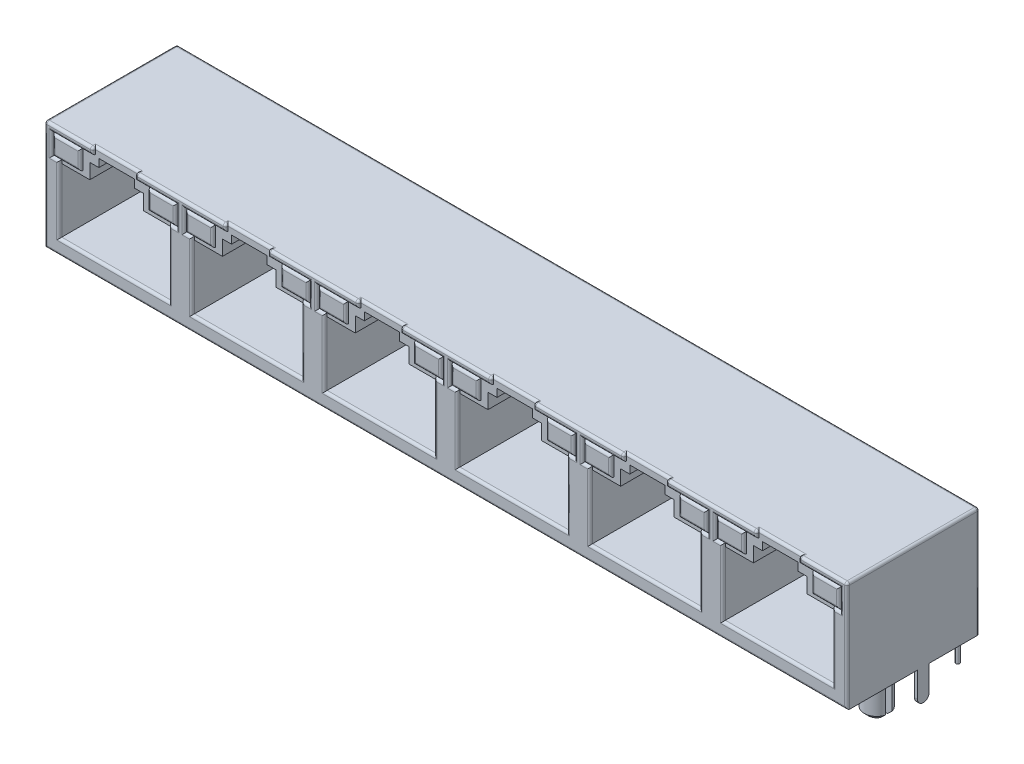
SolidWorks part; units mm, degrees
ref_plane "前视基准面" through (0, 0, 0) normal (0, 0, 1) x (1, 0, 0)
ref_plane "上视基准面" through (0, 0, 0) normal (0, 1, 0) x (1, 0, 0)
ref_plane "右视基准面" through (0, 0, 0) normal (1, 0, 0) x (0, 0, -1)
sketch "草图1" plane through (0, 0, 0) normal (0, 1, 0) x (1, 0, 0)
  line L0 (15.2703, 0) -> (110.5203, 0)
  line L1 (110.5203, 0) -> (110.5203, 15.7)
  line L2 (110.5203, 15.7) -> (15.2703, 15.7)
  line L3 (15.2703, 15.7) -> (15.2703, 0)
extrude "凸台-拉伸1" add sketch "草图1" along normal blind 13.05
sketch "草图2" plane through (0, 0, 0) normal (0, -1, 0) x (1, 0, 0)
  circle A0 centre (17.1703, -5.4) radius 1.48
  circle A1 centre (108.6203, -5.4) radius 1.48
extrude "凸台-拉伸2" add sketch "草图2" along normal blind 3.7
sketch "草图3" plane through (0, 0, 0) normal (0, 0, 1) x (1, 0, 0)
  line L0 (64.2703, 1.76) -> (77.2703, 1.76)
  line L3 (72.8703, 12.05) -> (68.6703, 12.05)
  line L4 (68.6703, 12.05) -> (68.6703, 11.11)
  line L5 (68.6703, 11.11) -> (67.5953, 11.11)
  line L6 (67.5953, 11.11) -> (67.5953, 9.32)
  line L7 (67.5953, 9.32) -> (64.2703, 9.32)
  line L8 (77.2703, 1.76) -> (77.2703, 9.32)
  line L10 (64.2703, 1.76) -> (64.2703, 9.32)
  line L11 (73.9453, 9.32) -> (77.2703, 9.32)
  line L12 (73.9453, 11.11) -> (73.9453, 9.32)
  line L13 (72.8703, 11.11) -> (73.9453, 11.11)
  line L14 (72.8703, 12.05) -> (72.8703, 11.11)
  line L15 (80.0203, 1.76) -> (93.0203, 1.76)
  line L16 (88.6203, 12.05) -> (84.4203, 12.05)
  line L17 (84.4203, 12.05) -> (84.4203, 11.11)
  line L18 (84.4203, 11.11) -> (83.3453, 11.11)
  line L19 (83.3453, 11.11) -> (83.3453, 9.32)
  line L20 (83.3453, 9.32) -> (80.0203, 9.32)
  line L21 (93.0203, 1.76) -> (93.0203, 9.32)
  line L22 (80.0203, 1.76) -> (80.0203, 9.32)
  line L23 (89.6953, 9.32) -> (93.0203, 9.32)
  line L24 (89.6953, 11.11) -> (89.6953, 9.32)
  line L25 (88.6203, 11.11) -> (89.6953, 11.11)
  line L26 (88.6203, 12.05) -> (88.6203, 11.11)
  line L27 (95.7703, 1.76) -> (108.7703, 1.76)
  line L28 (104.3703, 12.05) -> (100.1703, 12.05)
  line L29 (100.1703, 12.05) -> (100.1703, 11.11)
  line L30 (100.1703, 11.11) -> (99.0953, 11.11)
  line L31 (99.0953, 11.11) -> (99.0953, 9.32)
  line L32 (99.0953, 9.32) -> (95.7703, 9.32)
  line L33 (108.7703, 1.76) -> (108.7703, 9.32)
  line L34 (95.7703, 1.76) -> (95.7703, 9.32)
  line L35 (105.4453, 9.32) -> (108.7703, 9.32)
  line L36 (105.4453, 11.11) -> (105.4453, 9.32)
  line L37 (104.3703, 11.11) -> (105.4453, 11.11)
  line L38 (104.3703, 12.05) -> (104.3703, 11.11)
  line L39 (48.5203, 1.76) -> (61.5203, 1.76)
  line L40 (57.1203, 12.05) -> (52.9203, 12.05)
  line L41 (52.9203, 12.05) -> (52.9203, 11.11)
  line L42 (52.9203, 11.11) -> (51.8453, 11.11)
  line L43 (51.8453, 11.11) -> (51.8453, 9.32)
  line L44 (51.8453, 9.32) -> (48.5203, 9.32)
  line L45 (61.5203, 1.76) -> (61.5203, 9.32)
  line L46 (48.5203, 1.76) -> (48.5203, 9.32)
  line L47 (58.1953, 9.32) -> (61.5203, 9.32)
  line L48 (58.1953, 11.11) -> (58.1953, 9.32)
  line L49 (57.1203, 11.11) -> (58.1953, 11.11)
  line L50 (57.1203, 12.05) -> (57.1203, 11.11)
  line L51 (32.7703, 1.76) -> (45.7703, 1.76)
  line L52 (41.3703, 12.05) -> (37.1703, 12.05)
  line L53 (37.1703, 12.05) -> (37.1703, 11.11)
  line L54 (37.1703, 11.11) -> (36.0953, 11.11)
  line L55 (36.0953, 11.11) -> (36.0953, 9.32)
  line L56 (36.0953, 9.32) -> (32.7703, 9.32)
  line L57 (45.7703, 1.76) -> (45.7703, 9.32)
  line L58 (32.7703, 1.76) -> (32.7703, 9.32)
  line L59 (42.4453, 9.32) -> (45.7703, 9.32)
  line L60 (42.4453, 11.11) -> (42.4453, 9.32)
  line L61 (41.3703, 11.11) -> (42.4453, 11.11)
  line L62 (41.3703, 12.05) -> (41.3703, 11.11)
  line L63 (17.0203, 1.76) -> (30.0203, 1.76)
  line L64 (25.6203, 12.05) -> (21.4203, 12.05)
  line L65 (21.4203, 12.05) -> (21.4203, 11.11)
  line L66 (21.4203, 11.11) -> (20.3453, 11.11)
  line L67 (20.3453, 11.11) -> (20.3453, 9.32)
  line L68 (20.3453, 9.32) -> (17.0203, 9.32)
  line L69 (30.0203, 1.76) -> (30.0203, 9.32)
  line L70 (17.0203, 1.76) -> (17.0203, 9.32)
  line L71 (26.6953, 9.32) -> (30.0203, 9.32)
  line L72 (26.6953, 11.11) -> (26.6953, 9.32)
  line L73 (25.6203, 11.11) -> (26.6953, 11.11)
  line L74 (25.6203, 12.05) -> (25.6203, 11.11)
  dimension "D1" = 3
  dimension "D2" = 4
extrude "切除-拉伸1" cut sketch "草图3" against normal blind 13
sketch "草图4" plane through (0, 0, 0) normal (0, 0, 1) x (1, 0, 0)
  line L0 (21.0203, 13.05) -> (26.0203, 13.05)
  line L1 (15.2703, 13.05) -> (110.5203, 13.05) construction
  line L2 (26.0203, 12.25) -> (30.9203, 12.25)
  line L3 (30.9203, 12.25) -> (30.9203, 9.73)
  line L4 (30.9203, 9.73) -> (30.0203, 9.73)
  line L5 (30.0203, 9.73) -> (30.0203, 9.32)
  line L6 (17.0203, 9.32) -> (30.0203, 9.32)
  line L7 (26.0203, 13.05) -> (26.0203, 12.25)
  line L8 (21.0203, 13.05) -> (21.0203, 12.25)
  line L9 (17.0203, 9.73) -> (17.0203, 9.32)
  line L10 (16.1203, 9.73) -> (17.0203, 9.73)
  line L11 (16.1203, 12.25) -> (16.1203, 9.73)
  line L12 (21.0203, 12.25) -> (16.1203, 12.25)
  line L13 (36.7703, 13.05) -> (41.7703, 13.05)
  line L14 (41.7703, 12.25) -> (46.6703, 12.25)
  line L15 (46.6703, 12.25) -> (46.6703, 9.73)
  line L16 (46.6703, 9.73) -> (45.7703, 9.73)
  line L17 (45.7703, 9.73) -> (45.7703, 9.32)
  line L18 (32.7703, 9.32) -> (45.7703, 9.32)
  line L19 (41.7703, 13.05) -> (41.7703, 12.25)
  line L20 (36.7703, 13.05) -> (36.7703, 12.25)
  line L21 (32.7703, 9.73) -> (32.7703, 9.32)
  line L22 (31.8703, 9.73) -> (32.7703, 9.73)
  line L23 (31.8703, 12.25) -> (31.8703, 9.73)
  line L24 (36.7703, 12.25) -> (31.8703, 12.25)
  line L25 (52.5203, 13.05) -> (57.5203, 13.05)
  line L26 (57.5203, 12.25) -> (62.4203, 12.25)
  line L27 (62.4203, 12.25) -> (62.4203, 9.73)
  line L28 (62.4203, 9.73) -> (61.5203, 9.73)
  line L29 (61.5203, 9.73) -> (61.5203, 9.32)
  line L30 (48.5203, 9.32) -> (61.5203, 9.32)
  line L31 (57.5203, 13.05) -> (57.5203, 12.25)
  line L32 (52.5203, 13.05) -> (52.5203, 12.25)
  line L33 (48.5203, 9.73) -> (48.5203, 9.32)
  line L34 (47.6203, 9.73) -> (48.5203, 9.73)
  line L35 (47.6203, 12.25) -> (47.6203, 9.73)
  line L36 (52.5203, 12.25) -> (47.6203, 12.25)
  line L37 (68.2703, 13.05) -> (73.2703, 13.05)
  line L38 (73.2703, 12.25) -> (78.1703, 12.25)
  line L39 (78.1703, 12.25) -> (78.1703, 9.73)
  line L40 (78.1703, 9.73) -> (77.2703, 9.73)
  line L41 (77.2703, 9.73) -> (77.2703, 9.32)
  line L42 (64.2703, 9.32) -> (77.2703, 9.32)
  line L43 (73.2703, 13.05) -> (73.2703, 12.25)
  line L44 (68.2703, 13.05) -> (68.2703, 12.25)
  line L45 (64.2703, 9.73) -> (64.2703, 9.32)
  line L46 (63.3703, 9.73) -> (64.2703, 9.73)
  line L47 (63.3703, 12.25) -> (63.3703, 9.73)
  line L48 (68.2703, 12.25) -> (63.3703, 12.25)
  line L49 (84.0203, 13.05) -> (89.0203, 13.05)
  line L50 (89.0203, 12.25) -> (93.9203, 12.25)
  line L51 (93.9203, 12.25) -> (93.9203, 9.73)
  line L52 (93.9203, 9.73) -> (93.0203, 9.73)
  line L53 (93.0203, 9.73) -> (93.0203, 9.32)
  line L54 (80.0203, 9.32) -> (93.0203, 9.32)
  line L55 (89.0203, 13.05) -> (89.0203, 12.25)
  line L56 (84.0203, 13.05) -> (84.0203, 12.25)
  line L57 (80.0203, 9.73) -> (80.0203, 9.32)
  line L58 (79.1203, 9.73) -> (80.0203, 9.73)
  line L59 (79.1203, 12.25) -> (79.1203, 9.73)
  line L60 (84.0203, 12.25) -> (79.1203, 12.25)
  line L61 (99.7703, 13.05) -> (104.7703, 13.05)
  line L62 (104.7703, 12.25) -> (109.6703, 12.25)
  line L63 (109.6703, 12.25) -> (109.6703, 9.73)
  line L64 (109.6703, 9.73) -> (108.7703, 9.73)
  line L65 (108.7703, 9.73) -> (108.7703, 9.32)
  line L66 (95.7703, 9.32) -> (108.7703, 9.32)
  line L67 (104.7703, 13.05) -> (104.7703, 12.25)
  line L68 (99.7703, 13.05) -> (99.7703, 12.25)
  line L69 (95.7703, 9.73) -> (95.7703, 9.32)
  line L70 (94.8703, 9.73) -> (95.7703, 9.73)
  line L71 (94.8703, 12.25) -> (94.8703, 9.73)
  line L72 (99.7703, 12.25) -> (94.8703, 12.25)
  dimension "D1" = 6
extrude "切除-拉伸2" cut sketch "草图4" against normal blind 0.3
sketch "草图5" plane through (0, 0, -0.3) normal (0, 0, 1) x (1, 0, 0)
  line L1 (46.5703, 9.85) -> (46.5703, 12.15)
  line L6 (30.8203, 9.85) -> (30.8203, 12.15)
  line L7 (27.5203, 9.85) -> (30.8203, 9.85)
  line L8 (27.5203, 12.15) -> (27.5203, 9.85)
  line L9 (16.2203, 12.15) -> (19.5203, 12.15)
  line L10 (19.5203, 12.15) -> (19.5203, 9.85)
  line L11 (19.5203, 9.85) -> (16.2203, 9.85)
  line L12 (16.2203, 9.85) -> (16.2203, 12.15)
  line L13 (30.8203, 12.15) -> (27.5203, 12.15)
  line L14 (43.2703, 9.85) -> (46.5703, 9.85)
  line L15 (43.2703, 12.15) -> (43.2703, 9.85)
  line L16 (31.9703, 12.15) -> (35.2703, 12.15)
  line L17 (35.2703, 12.15) -> (35.2703, 9.85)
  line L18 (35.2703, 9.85) -> (31.9703, 9.85)
  line L19 (31.9703, 9.85) -> (31.9703, 12.15)
  line L20 (46.5703, 12.15) -> (43.2703, 12.15)
  line L21 (62.3203, 9.85) -> (62.3203, 12.15)
  line L22 (59.0203, 9.85) -> (62.3203, 9.85)
  line L23 (59.0203, 12.15) -> (59.0203, 9.85)
  line L24 (47.7203, 12.15) -> (51.0203, 12.15)
  line L25 (51.0203, 12.15) -> (51.0203, 9.85)
  line L26 (51.0203, 9.85) -> (47.7203, 9.85)
  line L27 (47.7203, 9.85) -> (47.7203, 12.15)
  line L28 (62.3203, 12.15) -> (59.0203, 12.15)
  line L29 (78.0703, 9.85) -> (78.0703, 12.15)
  line L30 (74.7703, 9.85) -> (78.0703, 9.85)
  line L31 (74.7703, 12.15) -> (74.7703, 9.85)
  line L32 (63.4703, 12.15) -> (66.7703, 12.15)
  line L33 (66.7703, 12.15) -> (66.7703, 9.85)
  line L34 (66.7703, 9.85) -> (63.4703, 9.85)
  line L35 (63.4703, 9.85) -> (63.4703, 12.15)
  line L36 (78.0703, 12.15) -> (74.7703, 12.15)
  line L37 (93.8203, 9.85) -> (93.8203, 12.15)
  line L38 (90.5203, 9.85) -> (93.8203, 9.85)
  line L39 (90.5203, 12.15) -> (90.5203, 9.85)
  line L40 (79.2203, 12.15) -> (82.5203, 12.15)
  line L41 (82.5203, 12.15) -> (82.5203, 9.85)
  line L42 (82.5203, 9.85) -> (79.2203, 9.85)
  line L43 (79.2203, 9.85) -> (79.2203, 12.15)
  line L44 (93.8203, 12.15) -> (90.5203, 12.15)
  line L45 (109.5703, 9.85) -> (109.5703, 12.15)
  line L46 (106.2703, 9.85) -> (109.5703, 9.85)
  line L47 (106.2703, 12.15) -> (106.2703, 9.85)
  line L48 (94.9703, 12.15) -> (98.2703, 12.15)
  line L49 (98.2703, 12.15) -> (98.2703, 9.85)
  line L50 (98.2703, 9.85) -> (94.9703, 9.85)
  line L51 (94.9703, 9.85) -> (94.9703, 12.15)
  line L52 (109.5703, 12.15) -> (106.2703, 12.15)
  dimension "D1" = 6
extrude "凸台-拉伸4" add sketch "草图5" along normal blind 0.3
fillet "圆角2" radius 0.3 48 edges at (106.2703, 11, 0) (107.9203, 12.15, 0) (109.5703, 11, 0) (107.9203, 9.85, 0) (96.6203, 9.85, 0) (94.9703, 11, 0) (96.6203, 12.15, 0) (98.2703, 11, 0) (90.5203, 11, 0) (92.1703, 12.15, 0) (93.8203, 11, 0) (92.1703, 9.85, 0) (80.8703, 9.85, 0) (79.2203, 11, 0) (80.8703, 12.15, 0) (82.5203, 11, 0) (74.7703, 11, 0) (76.4203, 12.15, 0) (78.0703, 11, 0) (76.4203, 9.85, 0) (65.1203, 9.85, 0) (63.4703, 11, 0) (65.1203, 12.15, 0) (66.7703, 11, 0) (59.0203, 11, 0) (60.6703, 12.15, 0) (62.3203, 11, 0) (60.6703, 9.85, 0) (49.3703, 9.85, 0) (47.7203, 11, 0) (49.3703, 12.15, 0) (51.0203, 11, 0) (43.2703, 11, 0) (44.9203, 12.15, 0) (46.5703, 11, 0) (44.9203, 9.85, 0) (33.6203, 9.85, 0) (31.9703, 11, 0) (33.6203, 12.15, 0) (35.2703, 11, 0) (27.5203, 11, 0) (29.1703, 12.15, 0) (30.8203, 11, 0) (29.1703, 9.85, 0) (17.8703, 9.85, 0) (16.2203, 11, 0) (17.8703, 12.15, 0) (19.5203, 11, 0)
sketch "草图8" plane through (15.2703, 0, 0) normal (-1, 0, 0) x (0, 0, 1)
  line L3 (-9.72, 0) -> (-9.72, -3.01)
  line L4 (-15.7, 0) -> (0, 0) construction
  line L5 (-9.72, 0) -> (-8.34, 0)
  line L9 (-8.34, 0) -> (-8.34, -3.01)
  arc A0 (-8.34, -3.01) -> (-9.72, -3.01) centre (-9.03, -3.01) cw
extrude "凸台-拉伸5" add sketch "草图8" against normal blind 0.35
sketch "草图9" plane through (110.5203, 0, 0) normal (1, 0, 0) x (0, 0, -1)
  line L3 (9.72, -3.01) -> (9.72, 0)
  line L4 (9.72, 0) -> (8.34, 0)
  line L5 (8.34, 0) -> (8.34, -3.01)
  line L6 (9.72, -3.01) -> (9.72, 0)
  line L7 (9.72, 0) -> (8.34, 0)
  line L8 (8.34, 0) -> (8.34, -3.01)
  arc A1 (8.34, -3.01) -> (9.72, -3.01) centre (9.03, -3.01) ccw
  arc A2 (8.34, -3.01) -> (9.72, -3.01) centre (9.03, -3.01) ccw
  dimension "D1" = 0
extrude "凸台-拉伸6" add sketch "草图9" against normal blind 0.35
sketch "草图10" plane through (0, 0, -15.7) normal (0, 0, -1) x (-1, 0, 0)
  line L0 (-54.2903, 0) -> (-55.7503, 0)
  line L1 (-110.5203, 0) -> (-15.2703, 0) construction
  line L2 (-70.0403, -2.97) -> (-70.0403, 0)
  line L3 (-54.2903, 0) -> (-54.2903, -2.97)
  line L5 (-55.7503, -2.97) -> (-55.7503, 0)
  line L7 (-71.5003, 0) -> (-71.5003, -2.97)
  line L8 (-71.5003, 0) -> (-70.0403, 0)
  arc A0 (-54.2903, -2.97) -> (-55.7503, -2.97) centre (-55.0203, -2.97) cw
  arc A1 (-71.5003, -2.97) -> (-70.0403, -2.97) centre (-70.7703, -2.97) ccw
extrude "凸台-拉伸7" add sketch "草图10" against normal blind 0.35
sketch "草图11" plane through (0, 0, 0) normal (0, -1, 0) x (1, 0, 0)
  line L0 (70.7703, -11.2) -> (66.8853, -11.2)
  line L2 (55.0203, -11.2) -> (51.1353, -11.2)
  line L3 (51.1353, -11.2) -> (51.1353, -15.7)
  line L4 (54.2903, -15.7) -> (15.2703, -15.7) construction
  line L5 (51.1353, -15.7) -> (54.2903, -15.7)
  line L6 (70.0403, -15.7) -> (55.7503, -15.7) construction
  line L7 (58.9053, -15.7) -> (58.9053, -11.2)
  line L8 (58.9053, -11.2) -> (55.0203, -11.2)
  line L9 (66.8853, -11.2) -> (66.8853, -15.7)
  line L10 (66.8853, -15.7) -> (70.0403, -15.7)
  line L11 (74.6553, -15.7) -> (74.6553, -11.2)
  line L12 (74.6553, -11.2) -> (70.7703, -11.2)
  line L13 (86.5203, -11.2) -> (82.6353, -11.2)
  line L14 (82.6353, -11.2) -> (82.6353, -15.7)
  line L15 (82.6353, -15.7) -> (90.4053, -15.7)
  line L16 (90.4053, -15.7) -> (90.4053, -11.2)
  line L17 (90.4053, -11.2) -> (86.5203, -11.2)
  line L18 (102.2703, -11.2) -> (98.3853, -11.2)
  line L19 (98.3853, -11.2) -> (98.3853, -15.7)
  line L20 (98.3853, -15.7) -> (106.1553, -15.7)
  line L21 (106.1553, -15.7) -> (106.1553, -11.2)
  line L22 (106.1553, -11.2) -> (102.2703, -11.2)
  line L23 (39.2703, -11.2) -> (35.3853, -11.2)
  line L24 (35.3853, -11.2) -> (35.3853, -15.7)
  line L25 (35.3853, -15.7) -> (43.1553, -15.7)
  line L26 (43.1553, -15.7) -> (43.1553, -11.2)
  line L27 (43.1553, -11.2) -> (39.2703, -11.2)
  line L28 (23.5203, -11.2) -> (19.6353, -11.2)
  line L29 (19.6353, -11.2) -> (19.6353, -15.7)
  line L30 (19.6353, -15.7) -> (27.4053, -15.7)
  line L31 (27.4053, -15.7) -> (27.4053, -11.2)
  line L32 (27.4053, -11.2) -> (23.5203, -11.2)
  line L33 (54.2903, -15.35) -> (54.2903, -15.7)
  line L34 (54.2903, -15.35) -> (55.7503, -15.35)
  line L35 (55.7503, -15.35) -> (55.7503, -15.7)
  line L36 (70.0403, -15.7) -> (70.0403, -15.35)
  line L37 (70.0403, -15.35) -> (71.5003, -15.35)
  line L38 (71.5003, -15.35) -> (71.5003, -15.7)
  line L39 (71.5003, -15.7) -> (74.6553, -15.7)
  line L40 (55.7503, -15.7) -> (58.9053, -15.7)
  dimension "D1" = 4
  dimension "D2" = 3
extrude "切除-拉伸4" cut sketch "草图11" against normal blind 1.65
sketch "草图12" plane through (0, 0, 0) normal (0, -1, 0) x (1, 0, 0)
  circle A2 centre (23.0103, -7.94) radius 0.225
  circle A3 centre (24.0303, -9.72) radius 0.225
  circle A4 centre (25.0503, -7.94) radius 0.225
  circle A5 centre (27.0903, -7.94) radius 0.225
  circle A6 centre (20.9703, -7.94) radius 0.225
  circle A7 centre (21.9903, -9.72) radius 0.225
  circle A8 centre (19.9503, -9.72) radius 0.225
  circle A9 centre (26.0703, -9.72) radius 0.225
  circle A10 centre (18.9503, -14.52) radius 0.225
  circle A11 centre (16.6603, -14.52) radius 0.225
  circle A12 centre (30.3803, -14.52) radius 0.225
  circle A13 centre (28.0903, -14.52) radius 0.225
  circle A14 centre (34.7003, -14.52) radius 0.225
  circle A15 centre (32.4103, -14.52) radius 0.225
  circle A16 centre (46.1303, -14.52) radius 0.225
  circle A17 centre (43.8403, -14.52) radius 0.225
  circle A18 centre (50.4503, -14.52) radius 0.225
  circle A19 centre (48.1603, -14.52) radius 0.225
  circle A20 centre (61.8803, -14.52) radius 0.225
  circle A21 centre (59.5903, -14.52) radius 0.225
  circle A22 centre (66.2003, -14.52) radius 0.225
  circle A23 centre (63.9103, -14.52) radius 0.225
  circle A24 centre (77.6303, -14.52) radius 0.225
  circle A25 centre (75.3403, -14.52) radius 0.225
  circle A26 centre (81.9503, -14.52) radius 0.225
  circle A27 centre (79.6603, -14.52) radius 0.225
  circle A28 centre (93.3803, -14.52) radius 0.225
  circle A29 centre (91.0903, -14.52) radius 0.225
  circle A30 centre (97.7003, -14.52) radius 0.225
  circle A31 centre (95.4103, -14.52) radius 0.225
  circle A32 centre (109.1303, -14.52) radius 0.225
  circle A33 centre (106.8403, -14.52) radius 0.225
  circle A34 centre (38.7603, -7.94) radius 0.225
  circle A35 centre (39.7803, -9.72) radius 0.225
  circle A36 centre (40.8003, -7.94) radius 0.225
  circle A37 centre (42.8403, -7.94) radius 0.225
  circle A38 centre (36.7203, -7.94) radius 0.225
  circle A39 centre (37.7403, -9.72) radius 0.225
  circle A40 centre (35.7003, -9.72) radius 0.225
  circle A41 centre (41.8203, -9.72) radius 0.225
  circle A42 centre (54.5103, -7.94) radius 0.225
  circle A43 centre (55.5303, -9.72) radius 0.225
  circle A44 centre (56.5503, -7.94) radius 0.225
  circle A45 centre (58.5903, -7.94) radius 0.225
  circle A46 centre (52.4703, -7.94) radius 0.225
  circle A47 centre (53.4903, -9.72) radius 0.225
  circle A48 centre (51.4503, -9.72) radius 0.225
  circle A49 centre (57.5703, -9.72) radius 0.225
  circle A50 centre (70.2603, -7.94) radius 0.225
  circle A51 centre (71.2803, -9.72) radius 0.225
  circle A52 centre (72.3003, -7.94) radius 0.225
  circle A53 centre (74.3403, -7.94) radius 0.225
  circle A54 centre (68.2203, -7.94) radius 0.225
  circle A55 centre (69.2403, -9.72) radius 0.225
  circle A56 centre (67.2003, -9.72) radius 0.225
  circle A57 centre (73.3203, -9.72) radius 0.225
  circle A58 centre (86.0103, -7.94) radius 0.225
  circle A59 centre (87.0303, -9.72) radius 0.225
  circle A60 centre (88.0503, -7.94) radius 0.225
  circle A61 centre (90.0903, -7.94) radius 0.225
  circle A62 centre (83.9703, -7.94) radius 0.225
  circle A63 centre (84.9903, -9.72) radius 0.225
  circle A64 centre (82.9503, -9.72) radius 0.225
  circle A65 centre (89.0703, -9.72) radius 0.225
  circle A66 centre (101.7603, -7.94) radius 0.225
  circle A67 centre (102.7803, -9.72) radius 0.225
  circle A68 centre (103.8003, -7.94) radius 0.225
  circle A69 centre (105.8403, -7.94) radius 0.225
  circle A70 centre (99.7203, -7.94) radius 0.225
  circle A71 centre (100.7403, -9.72) radius 0.225
  circle A72 centre (98.7003, -9.72) radius 0.225
  circle A73 centre (104.8203, -9.72) radius 0.225
  dimension "D1" = 3
  dimension "D3" = 6
  dimension "D2" = 2
  dimension "D4" = 6
extrude "凸台-拉伸8" add sketch "草图12" along normal blind 3.01
chamfer "倒角1" distance 0.5 angle 45 2 edges at (108.6203, -3.7, -6.88) (17.1703, -3.7, -6.88)
sketch "草图13" plane through (0, -3.7, 0) normal (0, -1, 0) x (1, 0, 0)
  line L1 (15.2703, -8.34) -> (15.2703, 0) construction
  line L2 (15.2703, -5.4) -> (15.2703, -5)
  line L3 (15.2703, -5) -> (110.5203, -5)
  line L4 (110.5203, 0) -> (110.5203, -8.34) construction
  line L5 (110.5203, -5) -> (110.5203, -5.8)
  line L6 (110.5203, -5.8) -> (15.2703, -5.8)
  line L7 (15.2703, -5.8) -> (15.2703, -5.4)
extrude "切除-拉伸5" cut sketch "草图13" against normal up to surface (3.7 mm away) up to face at (104.8203, 0, -9.495)
fillet "圆角3" radius 0.3 99 edges at (89.0203, 13.05, -0.15) (86.5203, 13.05, -0.3) (84.0203, 13.05, -0.15) (73.2703, 13.05, -0.15) (70.7703, 13.05, -0.3) (68.2703, 13.05, -0.15) (57.5203, 13.05, -0.15) (55.0203, 13.05, -0.3) (52.5203, 13.05, -0.15) (41.7703, 13.05, -0.15) (39.2703, 13.05, -0.3) (36.7703, 13.05, -0.15) (26.0203, 13.05, -0.15) (23.5203, 13.05, -0.3) (21.0203, 13.05, -0.15) (15.2703, 13.05, -7.85) (62.8953, 13.05, -15.7) (110.5203, 13.05, -7.85) (104.7703, 13.05, -0.15) (102.2703, 13.05, -0.3) (99.7703, 13.05, -0.15) (102.2703, 1.76, 0) (108.7703, 5.745, 0) (109.2203, 9.73, 0) (109.6703, 10.99, 0) (107.2203, 12.25, 0) (104.7703, 12.65, 0) (107.6453, 13.05, 0) (110.5203, 6.525, 0) (62.8953, 0, 0) (15.2703, 6.525, 0) (18.1453, 13.05, 0) (21.0203, 12.65, 0) (18.5703, 12.25, 0) (16.1203, 10.99, 0) (16.5703, 9.73, 0) (17.0203, 5.745, 0) (23.5203, 1.76, 0) (30.0203, 5.745, 0) (30.4703, 9.73, 0) (30.9203, 10.99, 0) (28.4703, 12.25, 0) (26.0203, 12.65, 0) (31.3953, 13.05, 0) (36.7703, 12.65, 0) (34.3203, 12.25, 0) (31.8703, 10.99, 0) (32.3203, 9.73, 0) (32.7703, 5.745, 0) (39.2703, 1.76, 0) (45.7703, 5.745, 0) (46.2203, 9.73, 0) (46.6703, 10.99, 0) (44.2203, 12.25, 0) (41.7703, 12.65, 0) (47.1453, 13.05, 0) (52.5203, 12.65, 0) (50.0703, 12.25, 0) (47.6203, 10.99, 0) (48.0703, 9.73, 0) (48.5203, 5.745, 0) (55.0203, 1.76, 0) (61.5203, 5.745, 0) (61.9703, 9.73, 0) (62.4203, 10.99, 0) (59.9703, 12.25, 0) (57.5203, 12.65, 0) (62.8953, 13.05, 0) (68.2703, 12.65, 0) (65.8203, 12.25, 0) (63.3703, 10.99, 0) (63.8203, 9.73, 0) (64.2703, 5.745, 0) (70.7703, 1.76, 0) (77.2703, 5.745, 0) (77.7203, 9.73, 0) (78.1703, 10.99, 0) (75.7203, 12.25, 0) (73.2703, 12.65, 0) (78.6453, 13.05, 0) (84.0203, 12.65, 0) (81.5703, 12.25, 0) (79.1203, 10.99, 0) (79.5703, 9.73, 0) (80.0203, 5.745, 0) (86.5203, 1.76, 0) (93.0203, 5.745, 0) (93.4703, 9.73, 0) (93.9203, 10.99, 0) (91.4703, 12.25, 0) (89.0203, 12.65, 0) (94.3953, 13.05, 0) (99.7703, 12.65, 0) (97.3203, 12.25, 0) (94.8703, 10.99, 0) (95.3203, 9.73, 0) (95.7703, 5.745, 0) (110.5203, 6.525, -15.7) (15.2703, 6.525, -15.7)
